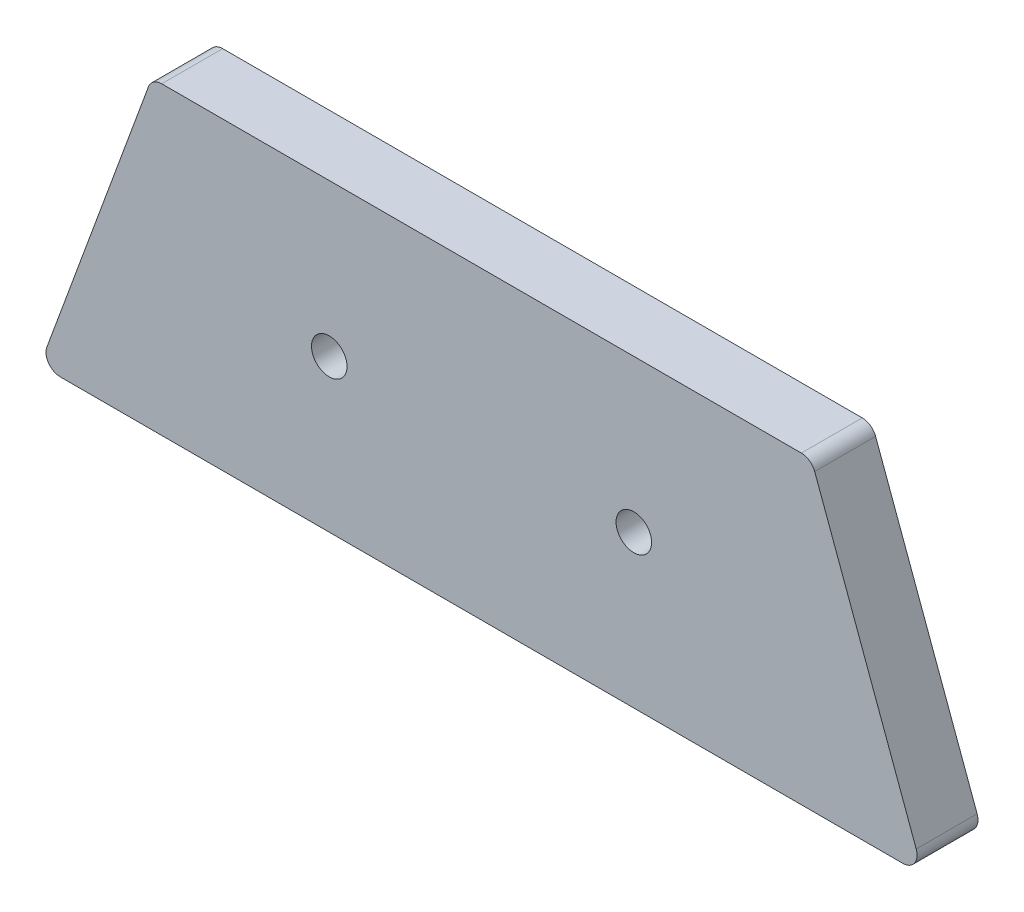
SolidWorks part; units mm, degrees
ref_plane "Front Plane" through (0, 0, 0) normal (0, 0, 1) x (1, 0, 0)
ref_plane "Top Plane" through (0, 0, 0) normal (0, 1, 0) x (1, 0, 0)
ref_plane "Right Plane" through (0, 0, 0) normal (1, 0, 0) x (0, 0, -1)
sketch "Sketch2" plane through (0, 0, 0) normal (0, 0, 1) x (1, 0, 0)
  line L0 (0, 84.074) -> (0, -72.39) construction
  line L1 (40.005, 34.1945) -> (-40.005, 34.1945)
  line L2 (52.705, -3.9055) -> (-52.705, -3.9055)
  line L3 (-54.3738, -1.514) -> (-41.6738, 33.03)
  line L4 (54.3738, -1.514) -> (41.6738, 33.03)
  arc A0 (-54.3738, -1.514) -> (-52.705, -3.9055) centre (-52.705, -2.1275) ccw
  arc A1 (-40.005, 34.1945) -> (-41.6738, 33.03) centre (-40.005, 32.4165) ccw
  arc A2 (54.3738, -1.514) -> (52.705, -3.9055) centre (52.705, -2.1275) cw
  arc A3 (40.005, 34.1945) -> (41.6738, 33.03) centre (40.005, 32.4165) cw
  circle A4 centre (-19.05, 15.1445) radius 2.2225
  circle A5 centre (19.05, 15.1445) radius 2.2225
  point P4 (0, 57.6776)
  point P9 (0, 19.5776)
  point P20 (0, -3.9055)
  dimension "D2" = 3.556
  dimension "D3" = 3.556
  dimension "D6" = 4.445
  dimension "D1" = 38.1
  dimension "D4" = 105.41
  dimension "D5" = 80.01
  dimension "D7" = 19.05
  dimension "D8" = 19.05
extrude "Boss-Extrude1" add sketch "Sketch2" along normal blind 7.62
